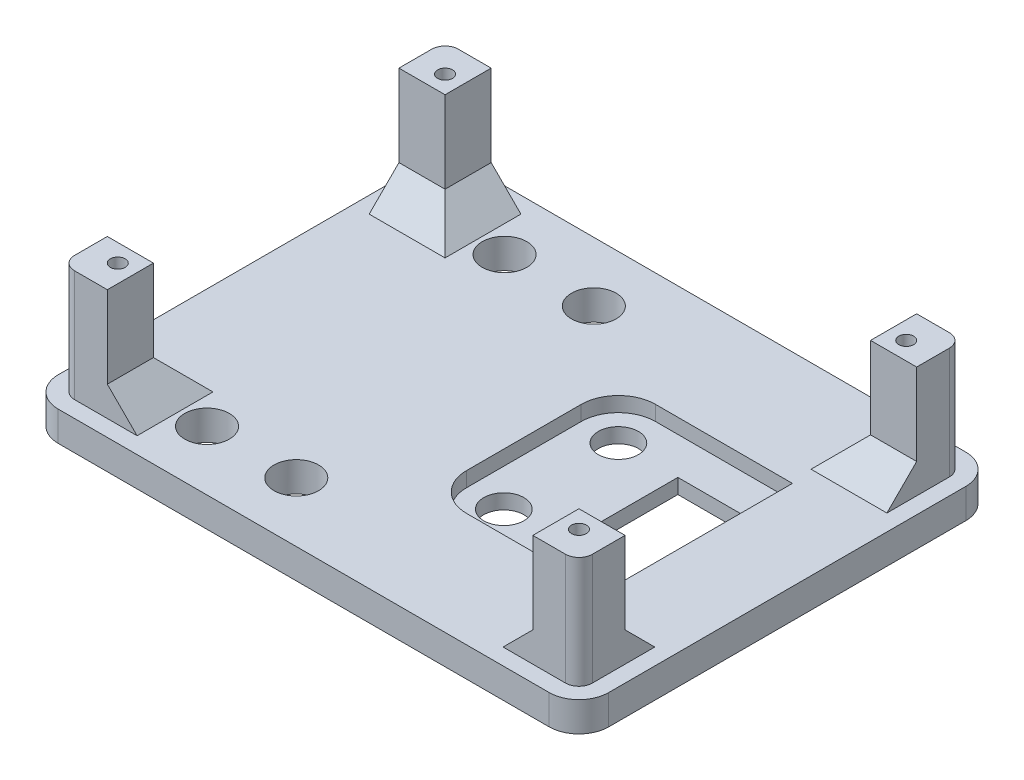
SolidWorks part; units mm, degrees
ref_plane "Front Plane" through (0, 0, 0) normal (0, 0, 1) x (1, 0, 0)
ref_plane "Top Plane" through (0, 0, 0) normal (0, 1, 0) x (1, 0, 0)
ref_plane "Right Plane" through (0, 0, 0) normal (1, 0, 0) x (0, 0, -1)
sketch "Sketch1" plane through (0, 0, 0) normal (0, 1, 0) x (1, 0, 0)
  line L1 (0, 0) -> (93.98, 0)
  line L2 (0, 0) -> (0, 71.12)
  line L3 (0, 71.12) -> (93.98, 71.12)
  line L4 (93.98, 0) -> (93.98, 71.12)
  dimension "D1" = 93.98
  dimension "D2" = 71.12
extrude "Boss-Extrude1" add sketch "Sketch1" along normal blind 5.08
sketch "Sketch2" plane through (0, 5.08, 0) normal (0, 1, 0) x (1, 0, 0)
  line L0 (46.99, 71.12) -> (46.99, 0) construction
  line L1 (2.794, 68.326) -> (10.668, 68.326)
  line L2 (2.794, 68.326) -> (2.794, 60.452)
  line L3 (2.794, 60.452) -> (10.668, 60.452)
  line L4 (10.668, 68.326) -> (10.668, 60.452)
  line L17 (93.98, 71.12) -> (0, 71.12) construction
  line L18 (0, 0) -> (93.98, 0) construction
  line L19 (0, 35.56) -> (93.98, 35.56) construction
  line L20 (0, 71.12) -> (0, 0) construction
  line L21 (93.98, 0) -> (93.98, 71.12) construction
  line L22 (83.312, 68.326) -> (83.312, 60.452)
  line L23 (91.186, 60.452) -> (83.312, 60.452)
  line L24 (91.186, 68.326) -> (91.186, 60.452)
  line L25 (91.186, 68.326) -> (83.312, 68.326)
  line L26 (91.186, 2.794) -> (83.312, 2.794)
  line L27 (91.186, 2.794) -> (91.186, 10.668)
  line L28 (91.186, 10.668) -> (83.312, 10.668)
  line L29 (83.312, 2.794) -> (83.312, 10.668)
  line L30 (10.668, 2.794) -> (10.668, 10.668)
  line L31 (2.794, 10.668) -> (10.668, 10.668)
  line L32 (2.794, 2.794) -> (2.794, 10.668)
  line L33 (2.794, 2.794) -> (10.668, 2.794)
  dimension "D1" = 7.874
  dimension "D2" = 7.874
  dimension "D3" = 2.794
  dimension "D4" = 2.794
fillet "Fillet4" radius 5.08 4 edges at (0, 2.54, -71.12) (93.98, 2.54, -71.12) (93.98, 2.54, 0) (0, 2.54, 0)
sketch "Sketch7" plane through (0, 5.08, 0) normal (0, 1, 0) x (1, 0, 0)
  line L0 (65.532, 35.56) -> (78.74, 35.56) construction
  line L1 (65.532, 45.339) -> (78.74, 45.339)
  line L2 (65.532, 45.339) -> (65.532, 25.781)
  line L3 (65.532, 25.781) -> (78.74, 25.781)
  line L4 (78.74, 45.339) -> (78.74, 25.781)
  circle A0 centre (55.372, 45.339) radius 3.429
  circle A1 centre (55.372, 25.781) radius 3.429
  dimension "D1" = 6.858
  dimension "D2" = 6.858
  dimension "D3" = 19.558
  dimension "D4" = 13.208
  dimension "D5" = 10.16
  dimension "D6" = 30.48
  dimension "D7" = 15.24
extrude "Cut-Extrude5" cut sketch "Sketch7" against normal up to next
sketch "Sketch8" plane through (0, 5.08, 0) normal (0, 1, 0) x (1, 0, 0)
  line L0 (5.08, 0) -> (88.9, 0) construction
  line L3 (0, 35.56) -> (93.98, 35.56) construction
  line L4 (0, 66.04) -> (0, 5.08) construction
  line L5 (93.98, 5.08) -> (93.98, 66.04) construction
  circle A2 centre (20.32, 10.16) radius 3.81
  circle A3 centre (35.56, 10.16) radius 3.81
  circle A4 centre (35.56, 60.96) radius 3.81
  circle A5 centre (20.32, 60.96) radius 3.81
  dimension "D1" = 15.24
  dimension "D2" = 7.62
  dimension "D4" = 7.62
  dimension "D3" = 10.16
  dimension "D5" = 15.24
sketch "Sketch9" plane through (0, 5.08, 0) normal (0, 1, 0) x (1, 0, 0)
  line L0 (55.372, 45.339) -> (55.372, 25.781) construction
  line L2 (49.022, 45.339) -> (49.022, 25.781)
  line L4 (65.532, 51.689) -> (78.74, 51.689)
  line L6 (65.532, 19.431) -> (78.74, 19.431)
  line L7 (78.74, 51.689) -> (78.74, 19.431)
  line L10 (78.74, 25.781) -> (78.74, 45.339) construction
  line L11 (55.372, 19.431) -> (65.532, 19.431)
  line L12 (55.372, 51.689) -> (65.532, 51.689)
  arc A0 (55.372, 51.689) -> (49.022, 45.339) centre (55.372, 45.339) ccw
  arc A1 (49.022, 25.781) -> (55.372, 19.431) centre (55.372, 25.781) ccw
  point P4 (55.372, 35.56)
  dimension "D2" = 6.35
  dimension "D3" = 6.35
extrude "Cut-Extrude7" cut sketch "Sketch9" against normal blind 2.54
extrude "Cut-Extrude8" cut sketch "Sketch8" against normal up to next
extrude "Boss-Extrude3" add sketch "Sketch2" along normal blind 30.48
sketch "Sketch10" plane through (0, 35.56, 0) normal (0, 1, 0) x (1, 0, 0)
  line L0 (46.99, 71.12) -> (46.99, 0) construction
  line L1 (88.9, 71.12) -> (5.08, 71.12) construction
  line L2 (5.08, 0) -> (88.9, 0) construction
  line L3 (0, 35.56) -> (93.98, 35.56) construction
  line L4 (0, 66.04) -> (0, 5.08) construction
  line L5 (93.98, 5.08) -> (93.98, 66.04) construction
  circle A0 centre (7.62, 63.5) radius 1.27
  circle A1 centre (86.36, 63.5) radius 1.27
  circle A2 centre (86.36, 7.62) radius 1.27
  circle A3 centre (7.62, 7.62) radius 1.27
  dimension "D1" = 7.62
  dimension "D3" = 2.54
  dimension "D2" = 7.62
extrude "Cut-Extrude9" cut sketch "Sketch10" against normal blind 12.7
fillet "Fillet5" radius 2.286 4 edges at (91.186, 20.32, -68.326) (91.186, 20.32, -2.794) (2.794, 20.32, -2.794) (2.794, 20.32, -68.326)
chamfer "Chamfer4" distance 5.08 angle 45 8 edges at (87.249, 5.08, -10.668) (83.312, 5.08, -6.731) (87.249, 5.08, -60.452) (83.312, 5.08, -64.389) (10.668, 5.08, -6.731) (6.731, 5.08, -10.668) (10.668, 5.08, -64.389) (6.731, 5.08, -60.452)
sketch "Sketch11" plane through (0, 35.56, 0) normal (0, 1, 0) x (1, 0, 0)
  line L1 (99.3383, -3.677) -> (-4.1971, -3.677)
  line L2 (99.3383, -3.677) -> (99.3383, 74.41)
  line L3 (99.3383, 74.41) -> (-4.1971, 74.41)
  line L4 (-4.1971, -3.677) -> (-4.1971, 74.41)
extrude "Cut-Extrude10" cut sketch "Sketch11" against normal blind 2.54
sketch "Sketch12" plane through (0, 33.02, 0) normal (0, 1, 0) x (1, 0, 0)
  line L1 (105.5236, -8.8567) -> (-21.2311, -8.8567)
  line L2 (105.5236, -8.8567) -> (105.5236, 83.8569)
  line L3 (105.5236, 83.8569) -> (-21.2311, 83.8569)
  line L4 (-21.2311, -8.8567) -> (-21.2311, 83.8569)
extrude "Cut-Extrude11" cut sketch "Sketch12" against normal blind 8.89
sketch "Sketch13" plane through (0, 24.13, 0) normal (0, 1, 0) x (1, 0, 0)
  circle A0 centre (86.36, 7.62) radius 1.27
  circle A1 centre (7.62, 7.62) radius 1.27
  circle A2 centre (86.36, 63.5) radius 1.27
  circle A3 centre (7.62, 63.5) radius 1.27
extrude "Cut-Extrude12" cut sketch "Sketch13" against normal blind 19.05
